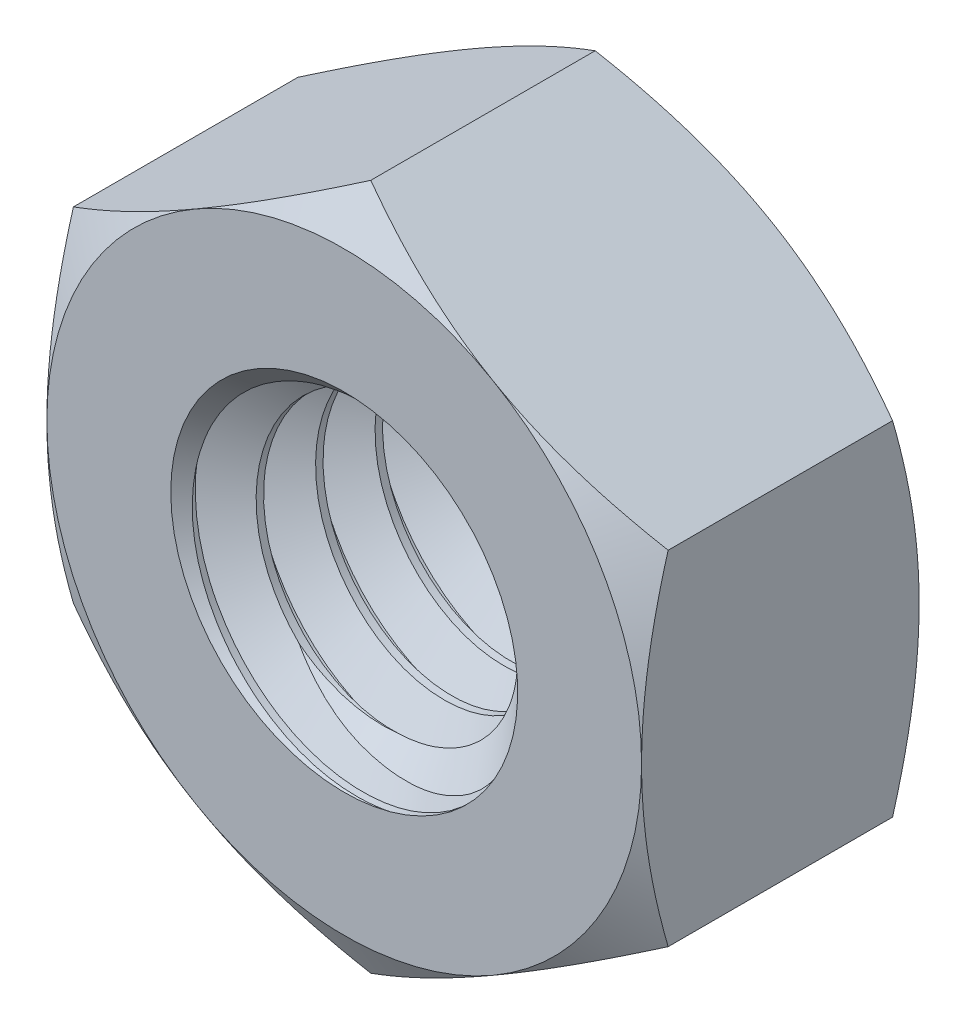
SolidWorks part; units mm, degrees
material "Stainless Steel (ferritic)"
ref_plane "Front" through (0, 0, 0) normal (0, 0, 1) x (1, 0, 0)
ref_plane "Top" through (0, 0, 0) normal (0, 1, 0) x (1, 0, 0)
ref_plane "Right" through (0, 0, 0) normal (1, 0, 0) x (0, 0, -1)
sketch "Sketch1" plane through (0, 0, 0) normal (0, 0, 1) x (1, 0, 0)
  line L1 (-3, 1.7321) -> (-3, -1.7321)
  line L2 (-3, -1.7321) -> (0, -3.4641)
  line L3 (0, -3.4641) -> (3, -1.7321)
  line L4 (3, -1.7321) -> (3, 1.7321)
  line L5 (3, 1.7321) -> (0, 3.4641)
  line L6 (0, 3.4641) -> (-3, 1.7321)
  circle A0 centre (0, 0) radius 3 construction
  circle A1 centre (0, 0) radius 1.75 construction
  point P10 (0, 1.75)
  dimension "hex" = 6
  dimension "dia" = 3.5
extrude "Extrude1" add sketch "Sketch1" along normal mid plane 2.8
sketch "Sketch4" plane through (0, 0, -1.4) normal (0, 0, -1) x (-1, 0, 0)
  circle A0 centre (0, 0) radius 1.75 construction
  circle A1 centre (0, 0) radius 1.75
sketch "Sketch10" plane through (0, 0, 1.4) normal (0, 0, 1) x (1, 0, 0)
  circle A0 centre (0, 0) radius 1.75 construction
  circle A1 centre (0, 0) radius 1.75
extrude "Cut-Extrude2" cut sketch "Sketch10" against normal through all draft 45
sketch "Sketch11" plane through (0, 0, -1.4) normal (0, 0, -1) x (-1, 0, 0)
  circle A0 centre (0, 0) radius 1.75 construction
  circle A1 centre (0, 0) radius 1.75
extrude "Cut-Extrude3" cut sketch "Sketch11" against normal through all draft 45
sketch "Sketch13" plane through (0, 0, -1.4) normal (0, 0, -1) x (-1, 0, 0)
  circle A0 centre (0, 0) radius 1.75 construction
  circle A1 centre (0, 0) radius 1.75
extrude "Boss-Extrude1" add sketch "Sketch13" against normal up to vertex (2.8 mm away) separate body up to point (-3, 1.732, 1.4)
curve "Helix/Spiral3" pitch 0.6 height 2.8 radius 1.75 centre (0, 0, -1.4) axis (0, 0, 1) start towards (0, 1, 0)
sketch "Sketch12" plane through (0, 0, 0) normal (1, 0, 0) x (0, 0, -1)
  line L0 (1.925, 1.75) -> (1.4, 1.75)
  line L1 (1.925, 1.75) -> (1.7, 1.3603)
  line L2 (1.7, 1.3603) -> (1.625, 1.3603)
  line L3 (1.625, 1.3603) -> (1.4, 1.75)
  line L4 (1.6625, 1.3603) -> (1.6625, 1.75) construction
  line L5 (1.5125, 1.5551) -> (1.8125, 1.5551) construction
  dimension "D1" = 60
  dimension "D2" = 0.075
  dimension "D3" = 0.3
sweep "Cut-Sweep1" cut profiles "Sketch12" path "Helix/Spiral3" align with end faces yes
combine bodies "Combine1" operation type subtract main body 116 bodies to subtract 118
sketch "Sketch7" plane through (0, 0, 1.4) normal (0, 0, 1) x (1, 0, 0)
  circle A0 centre (0, 0) radius 3 construction
  circle A1 centre (0, 0) radius 3
extrude "Extrude2" cut sketch "Sketch7" against normal blind 25.4 draft 60 flip side to cut
mirror "Mirror2" about plane through (0, 0, 0) normal (0, 0, 1) of "Extrude2"
sketch "Sketch8" plane through (0, 0, 1.4) normal (0, 0, 1) x (1, 0, 0)
  line L0 (-1.2374, 1.2374) -> (0, 0) construction
  line L1 (0, -1.8057) -> (0, 1.8057) construction
  circle A1 centre (0, 0) radius 1.75 construction
  point P0 (-1.2374, 1.2374)
  dimension "D1" = 45
sketch "Sketch14" plane through (0, 0, 1.4) normal (0, 0, 1) x (1, 0, 0)
  line L0 (0, 0) -> (-1.75, 0) construction
  arc A0 (0.4683, -1.6862) -> (1.5155, -0.875) centre (0, 0) ccw construction
equation "\"D3@Helix/Spiral3\" = \"length@Extrude1\" "
equation "\"D2@Sketch12\" = \"D4@Helix/Spiral3\"*.125"
equation "\"D3@Sketch12\" = \"D4@Helix/Spiral3\"*.50"
